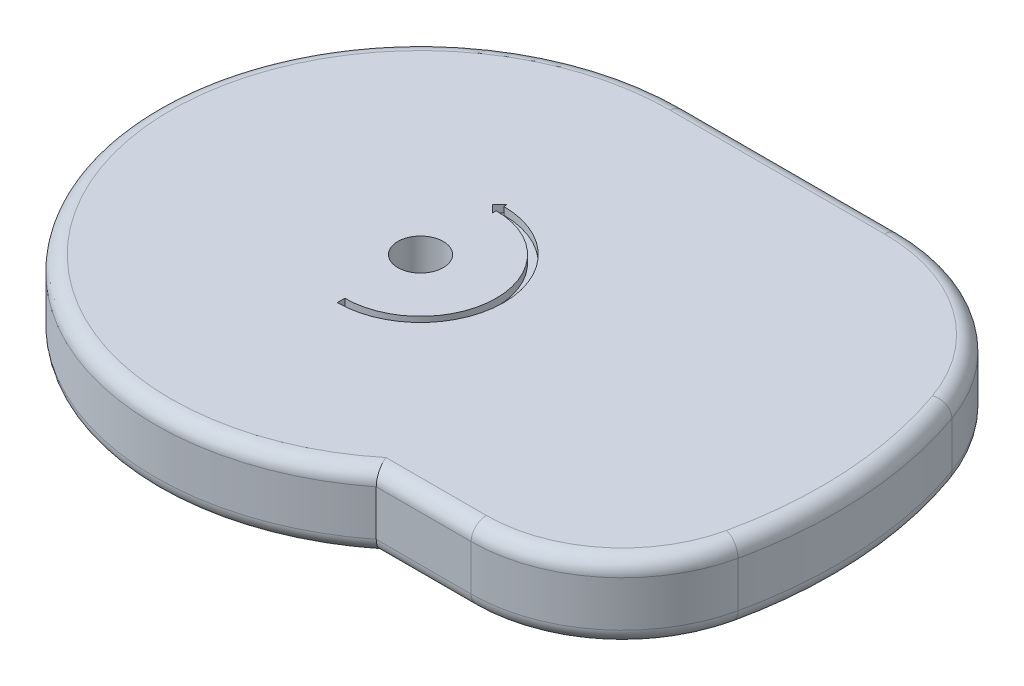
SolidWorks part; units mm, degrees
ref_plane "前基準面" through (0, 0, 0) normal (0, 0, 1) x (1, 0, 0)
ref_plane "上基準面" through (0, 0, 0) normal (0, 1, 0) x (1, 0, 0)
ref_plane "右基準面" through (0, 0, 0) normal (1, 0, 0) x (0, 0, -1)
sketch "草圖1" plane through (0, 0, 0) normal (0, 1, 0) x (1, 0, 0)
  line L0 (0, 35) -> (28.2843, 35)
  line L1 (0, -67.184) -> (0, 71.5631) construction
  line L2 (0, 0) -> (65.272, -37.6848) construction
  line L3 (34.187, -27.5) -> (21.6506, -27.5)
  line L4 (-50.4152, 0) -> (84.1624, 0) construction
  circle A0 centre (0, 0) radius 3
  arc A1 (0, 35) -> (21.6506, -27.5) centre (0, 0) ccw
  arc A2 (53.7224, -11.7857) -> (51.8545, 18.3333) centre (0, 0) ccw
  arc A3 (28.2843, 35) -> (51.8545, 18.3333) centre (28.2843, 10) cw
  arc A4 (34.187, -27.5) -> (53.7224, -11.7857) centre (34.187, -7.5) ccw
  point P14 (47.6314, -27.5)
  point P15 (55, 0)
  dimension "D1" = 70
  dimension "D2" = 110
  dimension "D3" = 6
  dimension "D5" = 25
  dimension "D7" = 20
  dimension "D8" = 55
  dimension "D4" = 120
  dimension "D6" = 30
extrude "填料-伸長1" add sketch "草圖1" along normal blind 10
fillet "圓角1" radius 2 12 edges at (14.1421, 0, -35) (42.718, 0, -30.4124) (54.8945, 0, -3.4044) (27.9188, 0, 27.5) (46.7226, 0, 23.0839) (-33.0719, 0, 11.4564) (54.8945, 10, -3.4044) (42.718, 10, -30.4124) (14.1421, 10, -35) (27.9188, 10, 27.5) (46.7226, 10, 23.0839) (-33.0719, 10, 11.4564)
sketch "草圖2" plane through (0, 10, 0) normal (0, 1, 0) x (1, 0, 0)
  line L4 (0, -10) -> (0, -11)
  line L5 (0, 11) -> (0, 10) construction
  line L7 (0, 11) -> (0, 11.5)
  line L8 (0, 11.5) -> (-1, 10.5)
  line L9 (-1, 10.5) -> (0, 9.5)
  line L10 (0, 9.5) -> (0, 10)
  line L11 (0.6189, 10.5) -> (-3.7232, 10.5) construction
  arc A0 (0, -10) -> (0, 10) centre (0, 0) ccw
  arc A1 (0, -11) -> (0, 11) centre (0, 0) ccw
  circle A2 centre (0, 0) radius 11 construction
  circle A3 centre (0, 0) radius 10 construction
  point P5 (0, 0)
  point P6 (0, 10.5)
  point P8 (-1.944, 10.5)
  dimension "D1" = 20
  dimension "D2" = 1
  dimension "D3" = 1
extrude "除料-伸長1" cut sketch "草圖2" against normal blind 1
